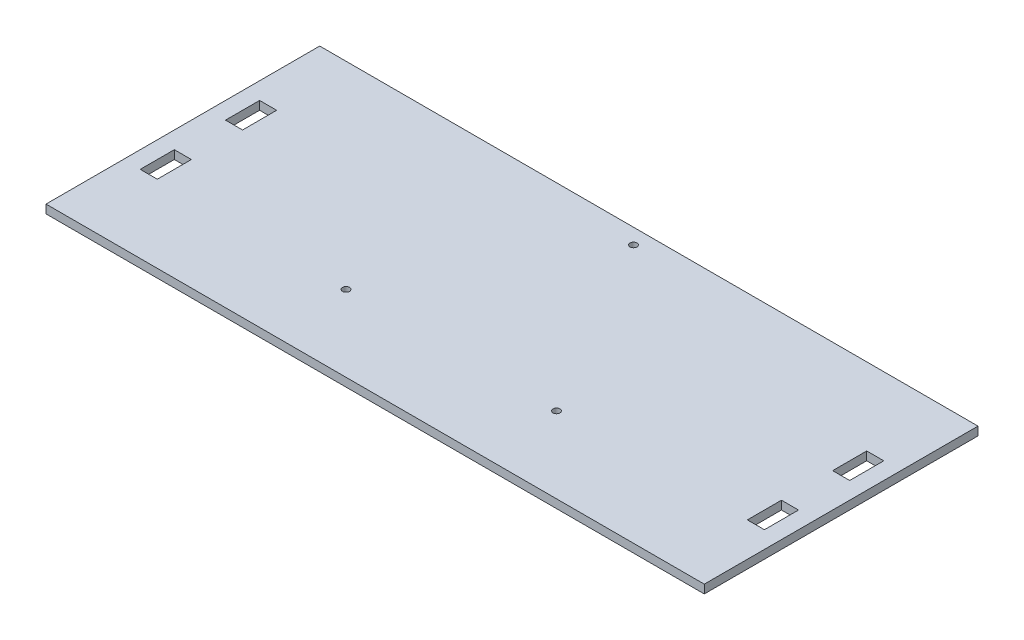
SolidWorks part; units mm, degrees
ref_plane "前基準面" through (0, 0, 0) normal (0, 0, 1) x (1, 0, 0)
ref_plane "上基準面" through (0, 0, 0) normal (0, 1, 0) x (1, 0, 0)
ref_plane "右基準面" through (0, 0, 0) normal (1, 0, 0) x (0, 0, -1)
sketch "草圖1" plane through (0, 0, 0) normal (0, 1, 0) x (1, 0, 0)
  line L0 (0, 0) -> (0, 89.692) construction
  line L1 (0, 0) -> (84.1488, -48.5834) construction
  line L2 (0, 0) -> (-79.0259, -45.6256) construction
  line L3 (183, -15) -> (173, -15)
  line L4 (193, -80.25) -> (-193, -80.25)
  line L5 (193, -80.25) -> (193, 80.25)
  line L6 (193, 80.25) -> (-193, 80.25)
  line L7 (-193, -80.25) -> (-193, 80.25)
  line L8 (0, 80.25) -> (0, -80.25) construction
  line L9 (193, 0) -> (-193, 0) construction
  line L10 (-155, -100) -> (155, -100) construction
  line L11 (-155, -100) -> (-155, 100) construction
  line L12 (-155, 100) -> (155, 100) construction
  line L13 (155, -100) -> (155, 100) construction
  line L14 (0, 100) -> (0, -100) construction
  line L15 (-155, 0) -> (155, 0) construction
  line L16 (-156, -22) -> (-172, -22) construction
  line L17 (-156, -22) -> (-156, 22) construction
  line L18 (-156, 22) -> (-172, 22) construction
  line L19 (-172, -22) -> (-172, 22) construction
  line L20 (-173, -50) -> (-183, -50) construction
  line L21 (-156, 0) -> (-172, 0) construction
  line L22 (-173, -50) -> (-173, 50) construction
  line L23 (-173, 50) -> (-183, 50) construction
  line L24 (-183, -50) -> (-183, 50) construction
  line L25 (-183, -35) -> (-173, -35)
  line L26 (-173, 0) -> (-183, 0) construction
  line L27 (-183, -35) -> (-183, -15)
  line L28 (-183, -15) -> (-173, -15)
  line L29 (-173, -35) -> (-173, -15)
  line L30 (-183, 15) -> (-173, 15)
  line L31 (-183, 15) -> (-183, 35)
  line L32 (-183, 35) -> (-173, 35)
  line L33 (-173, 15) -> (-173, 35)
  line L34 (173, -35) -> (173, -15)
  line L35 (183, -35) -> (173, -35)
  line L36 (183, -35) -> (183, -15)
  line L37 (183, 35) -> (173, 35)
  line L38 (173, 15) -> (173, 35)
  line L39 (183, 15) -> (173, 15)
  line L40 (183, 15) -> (183, 35)
  circle A0 centre (0, 71.25) radius 4 construction
  circle A4 centre (61.7043, -35.625) radius 4 construction
  circle A6 centre (-61.7043, -35.625) radius 4 construction
  circle A7 centre (0, 71.25) radius 2.05
  circle A8 centre (61.7043, -35.625) radius 2.05
  circle A9 centre (-61.7043, -35.625) radius 2.05
  circle A11 centre (0, 0) radius 75.25 construction
  circle A12 centre (0, 0) radius 80.25 construction
  point P22 (-164, 0)
  point P33 (-178, 0)
  dimension "D3" = 4.1
  dimension "D4" = 8
  dimension "D5" = 71.25
  dimension "D6" = 120
  dimension "D1" = 120
  dimension "D9" = 5
  dimension "D22" = 4.1
  dimension "D2" = 71.25
  dimension "D7" = 71.25
  dimension "D8" = 310
  dimension "D10" = 200
  dimension "D11" = 16
  dimension "D12" = 44
  dimension "D13" = 1
  dimension "D14" = 10
  dimension "D15" = 100
  dimension "D16" = 1
  dimension "D17" = 10
  dimension "D18" = 386
  dimension "D19" = 20
  dimension "D20" = 15
  dimension "D21" = 15
extrude "填料-伸長1" add sketch "草圖1" along normal blind 5
sketch "草圖2" plane through (0, 5, 0) normal (0, 1, 0) x (1, 0, 0)
  line L0 (-232.8206, 0) -> (229.5414, 0) construction
  line L1 (0, 102.2006) -> (0, -106.5728) construction
  line L2 (-56.9, 28.5) -> (-152.9, 28.5)
  line L3 (-56.9, 28.5) -> (-56.9, -28.5)
  line L4 (-56.9, -28.5) -> (-152.9, -28.5)
  line L5 (-152.9, 28.5) -> (-152.9, -28.5)
  line L6 (-104.9, -28.5) -> (-104.9, 28.5) construction
  line L7 (-56.9, 0) -> (-152.9, 0) construction
  line L8 (-173, -35) -> (-173, -15) construction
  line L9 (-173.9, 4) -> (-152.9, 4)
  line L10 (-173.9, 4) -> (-173.9, -4)
  line L11 (-173.9, -4) -> (-152.9, -4)
  line L12 (-152.9, 4) -> (-152.9, -4)
  line L13 (-172, 15) -> (-154.9, 15)
  line L14 (-173.9, 0) -> (-152.9, 0) construction
  line L15 (-172, 15) -> (-172, -15)
  line L16 (-172, -15) -> (-154.9, -15)
  line L17 (-154.9, 15) -> (-154.9, -15)
  line L18 (172, -15) -> (154.9, -15)
  line L19 (154.9, 15) -> (154.9, -15)
  line L20 (172, 15) -> (154.9, 15)
  line L21 (172, 15) -> (172, -15)
  line L22 (173.9, -4) -> (152.9, -4)
  line L23 (152.9, 4) -> (152.9, -4)
  line L24 (173.9, 4) -> (152.9, 4)
  line L25 (173.9, 4) -> (173.9, -4)
  line L26 (56.9, -28.5) -> (152.9, -28.5)
  line L27 (152.9, 28.5) -> (152.9, -28.5)
  line L28 (56.9, 28.5) -> (152.9, 28.5)
  line L29 (56.9, 28.5) -> (56.9, -28.5)
  point P3 (-104.9, 0)
  point P9 (-160.2566, 0)
  point P16 (-172, 0)
  dimension "D1" = 96
  dimension "D2" = 57
  dimension "D3" = 21
  dimension "D4" = 8
  dimension "D5" = 30
  dimension "D6" = 17.1
  dimension "D7" = 2
  dimension "D8" = 1
